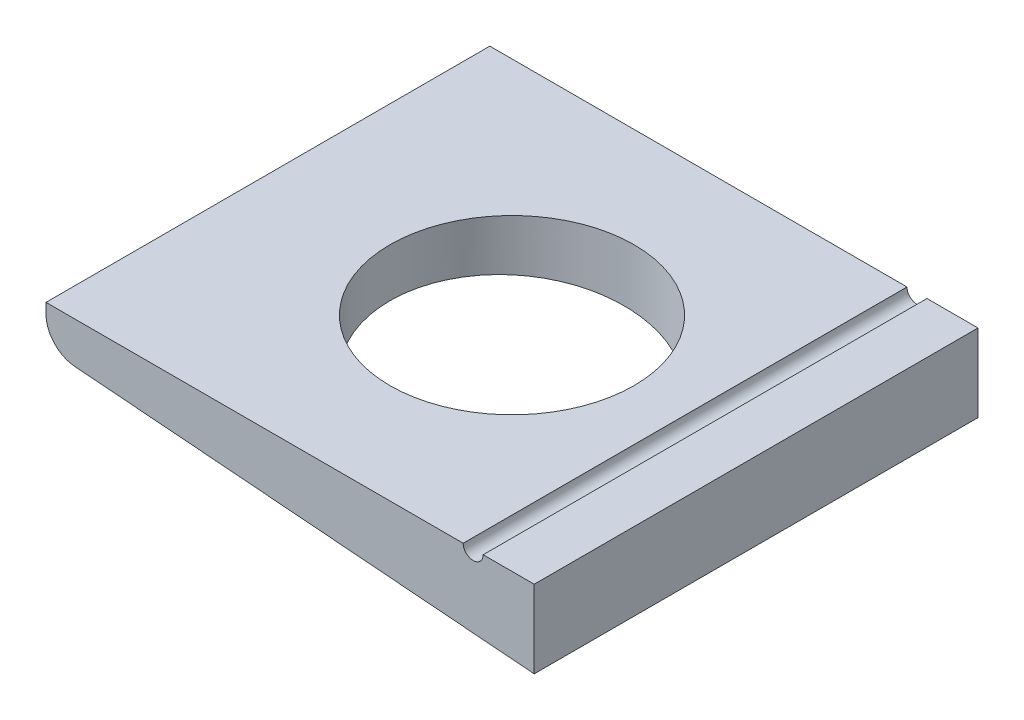
SolidWorks part; units mm, degrees
extrude "Base-Extrude" add sketch "Sketch1" along normal mid plane 40
sketch "Sketch1" plane through (0, 0, 0) normal (0, 0, 1) x (1, 0, 0)
  line L0 (22, 0) -> (-22, 0)
  line L1 (22, 0) -> (22, -7)
  line L2 (-22, 0) -> (-22, -0.9139)
  line L3 (22, -7) -> (-19.422, -3.7051)
  line L4 (0, 0) -> (0, -5.25) construction
  arc A0 (-19.422, -3.7051) -> (-22, -0.9139) centre (-19.2, -0.9139) cw
  dimension "D2" = 22
ref_plane "Plane1" through (0, 0, 0) normal (0, 0, 1) x (1, 0, 0)
ref_plane "Plane2" through (0, 0, 0) normal (0, 1, 0) x (1, 0, 0)
ref_plane "Plane3" through (0, 0, 0) normal (1, 0, 0) x (0, 0, -1)
sketch "Sketch2" plane through (0, 0, 0) normal (0, 1, 0) x (-1, 0, 0)
  circle A0 centre (0, 0) radius 11
extrude "Cut-Extrude1" cut sketch "Sketch2" against normal through all
sketch "Sketch3" plane through (0, 0, 20) normal (0, 0, 1) x (1, 0, 0)
  line L0 (22, 0) -> (-22, 0) construction
  circle A0 centre (16.5, 0) radius 0.9
  dimension "T" = 0.9
  dimension "D2" = 16.5
extrude "ID-Grooves" cut sketch "Sketch3" against normal through all
equation "\"D2@Sketch1\" = \"B@Sketch1\" / 2"
equation "\"D2@Sketch3\" =  ( \"D@Sketch2\" / 2 )  +  ( \"B@Sketch1\" -  \"D@Sketch2\" )  / 4"
